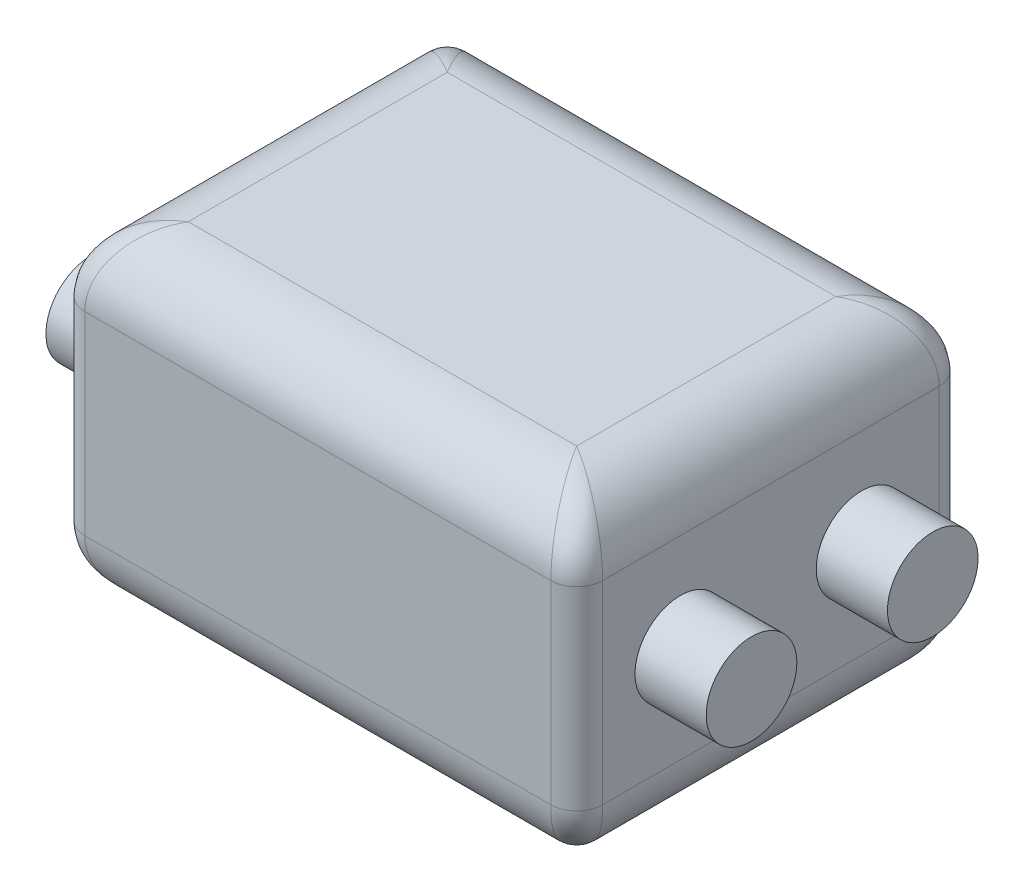
SolidWorks part; units mm, degrees
material "1060-H12"
ref_plane "Alzado" through (0, 0, 0) normal (0, 0, 1) x (1, 0, 0)
ref_plane "Planta" through (0, 0, 0) normal (0, 1, 0) x (1, 0, 0)
ref_plane "Vista lateral" through (0, 0, 0) normal (1, 0, 0) x (0, 0, -1)
sketch "Croquis1" plane through (0, 0, 0) normal (0, 1, 0) x (1, 0, 0)
  line L1 (-200, -150) -> (200, -150)
  line L2 (-200, -150) -> (-200, 150)
  line L3 (-200, 150) -> (200, 150)
  line L4 (200, -150) -> (200, 150)
  line L5 (-200, -150) -> (200, 150) construction
  line L6 (-200, 150) -> (200, -150) construction
  point P0 (0, 0)
  dimension "D1" = 300
  dimension "D2" = 400
extrude "Saliente-Extruir1" add sketch "Croquis1" along normal blind 125 and the other way blind 125
sketch "Croquis2" plane through (200, 0, 0) normal (1, 0, 0) x (0, 0, -1)
  line L0 (-150, 0) -> (150, 0) construction
  line L1 (-150, 125) -> (-150, -125) construction
  line L2 (150, 125) -> (150, -125) construction
  line L3 (0, -125) -> (0, 125) construction
  line L4 (-150, -125) -> (150, -125) construction
  line L5 (-150, 125) -> (150, 125) construction
  circle A0 centre (-70, 0) radius 35
  circle A1 centre (70, 0) radius 35
  dimension "D2" = 70
  dimension "D1" = 70
extrude "Saliente-Extruir2" add sketch "Croquis2" along normal blind 55
mirror "Simetría1" about plane through (0, 0, 0) normal (1, 0, 0) of "Saliente-Extruir2"
fillet "Redondeo1" radius 50 8 edges at (0, 125, 150) (-200, 125, 0) (0, 125, -150) (200, 125, 0) (-200, -125, 0) (0, -125, 150) (200, -125, 0) (0, -125, -150)
fillet "Redondeo2" radius 20 12 edges at (185.3553, 110.3553, 135.3553) (185.3553, -110.3553, 135.3553) (185.3553, 110.3553, -135.3553) (185.3553, -110.3553, -135.3553) (-185.3553, 110.3553, -135.3553) (-185.3553, -110.3553, -135.3553) (-185.3553, 110.3553, 135.3553) (-185.3553, -110.3553, 135.3553) (200, 0, 150) (200, 0, -150) (-200, 0, -150) (-200, 0, 150)
sketch "Croquis3" plane through (200, 0, 0) normal (1, 0, 0) x (0, 0, -1)
  line L0 (0, 0) -> (0, -600) construction
  dimension "D1" = 600
